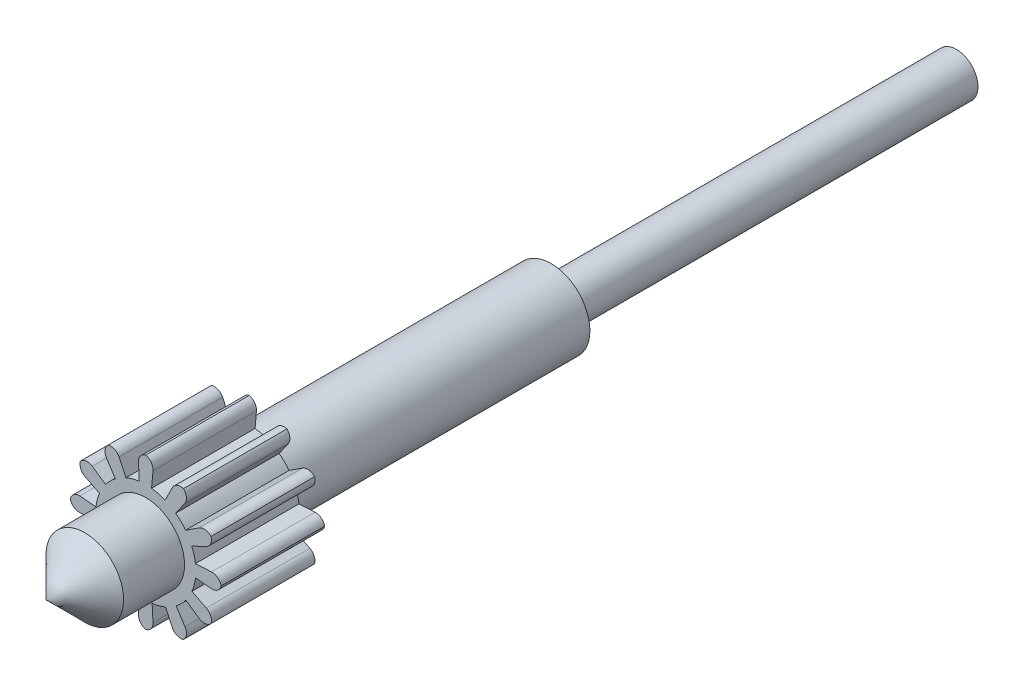
SolidWorks part; units mm, degrees
material "AISI 316 Stainless Steel Sheet (SS)"
ref_plane "Front Plane" through (0, 0, 0) normal (0, 0, 1) x (1, 0, 0)
ref_plane "Top Plane" through (0, 0, 0) normal (0, 1, 0) x (1, 0, 0)
ref_plane "Right Plane" through (0, 0, 0) normal (1, 0, 0) x (0, 0, -1)
sketch "Sketch1" plane through (0, 0, 0) normal (0, 0, 1) x (1, 0, 0)
  line L0 (0, 0) -> (0, 2.1618) construction
  line L1 (-0.1485, 1.153) -> (-0.1685, 1.5258)
  line L2 (0.1359, 1.1545) -> (0.1685, 1.5258)
  line L3 (0.4479, 1.0728) -> (0.617, 1.4056)
  line L4 (0.695, 0.9319) -> (0.9088, 1.2371)
  line L5 (0.9242, 0.7051) -> (1.2371, 0.9088)
  line L6 (1.0678, 0.4596) -> (1.4056, 0.617)
  line L7 (1.153, 0.1485) -> (1.5258, 0.1685)
  line L8 (1.1545, -0.1359) -> (1.5258, -0.1685)
  line L9 (1.0728, -0.4479) -> (1.4056, -0.617)
  line L10 (0.9319, -0.695) -> (1.2371, -0.9088)
  line L11 (0.7051, -0.9242) -> (0.9088, -1.2371)
  line L12 (0.4596, -1.0678) -> (0.617, -1.4056)
  line L13 (0.1485, -1.153) -> (0.1685, -1.5258)
  line L14 (-0.1359, -1.1545) -> (-0.1685, -1.5258)
  line L15 (-0.4479, -1.0728) -> (-0.617, -1.4056)
  line L16 (-0.695, -0.9319) -> (-0.9088, -1.2371)
  line L17 (-0.9242, -0.7051) -> (-1.2371, -0.9088)
  line L18 (-1.0678, -0.4596) -> (-1.4056, -0.617)
  line L19 (-1.153, -0.1485) -> (-1.5258, -0.1685)
  line L20 (-1.1545, 0.1359) -> (-1.5258, 0.1685)
  line L21 (-1.0728, 0.4479) -> (-1.4056, 0.617)
  line L22 (-0.9319, 0.695) -> (-1.2371, 0.9088)
  line L23 (-0.7051, 0.9242) -> (-0.9088, 1.2371)
  line L24 (-0.4596, 1.0678) -> (-0.617, 1.4056)
  arc A0 (-0.1485, 1.153) -> (-0.4596, 1.0678) centre (0, 0) ccw
  arc A1 (-0.7051, 0.9242) -> (-0.9319, 0.695) centre (0, 0) ccw
  arc A2 (0.4479, 1.0728) -> (0.1359, 1.1545) centre (0, 0) ccw
  arc A3 (-0.1685, 1.5258) -> (0, 1.75) centre (0.0494, 1.5375) cw
  arc A4 (0.1685, 1.5258) -> (0, 1.75) centre (-0.0494, 1.5375) ccw
  arc A5 (0.617, 1.4056) -> (0.875, 1.5155) centre (0.8115, 1.3068) cw
  arc A6 (0.9088, 1.2371) -> (0.875, 1.5155) centre (0.726, 1.3562) ccw
  arc A7 (1.2371, 0.9088) -> (1.5155, 0.875) centre (1.3562, 0.726) cw
  arc A8 (1.4056, 0.617) -> (1.5155, 0.875) centre (1.3068, 0.8115) ccw
  arc A9 (1.5258, 0.1685) -> (1.75, 0) centre (1.5375, -0.0494) cw
  arc A10 (1.5258, -0.1685) -> (1.75, 0) centre (1.5375, 0.0494) ccw
  arc A11 (1.4056, -0.617) -> (1.5155, -0.875) centre (1.3068, -0.8115) cw
  arc A12 (1.2371, -0.9088) -> (1.5155, -0.875) centre (1.3562, -0.726) ccw
  arc A13 (0.9088, -1.2371) -> (0.875, -1.5155) centre (0.726, -1.3562) cw
  arc A14 (0.617, -1.4056) -> (0.875, -1.5155) centre (0.8115, -1.3068) ccw
  arc A15 (0.1685, -1.5258) -> (0, -1.75) centre (-0.0494, -1.5375) cw
  arc A16 (-0.1685, -1.5258) -> (0, -1.75) centre (0.0494, -1.5375) ccw
  arc A17 (-0.617, -1.4056) -> (-0.875, -1.5155) centre (-0.8115, -1.3068) cw
  arc A18 (-0.9088, -1.2371) -> (-0.875, -1.5155) centre (-0.726, -1.3562) ccw
  arc A19 (-1.2371, -0.9088) -> (-1.5155, -0.875) centre (-1.3562, -0.726) cw
  arc A20 (-1.4056, -0.617) -> (-1.5155, -0.875) centre (-1.3068, -0.8115) ccw
  arc A21 (-1.5258, -0.1685) -> (-1.75, 0) centre (-1.5375, 0.0494) cw
  arc A22 (-1.5258, 0.1685) -> (-1.75, 0) centre (-1.5375, -0.0494) ccw
  arc A23 (-1.4056, 0.617) -> (-1.5155, 0.875) centre (-1.3068, 0.8115) cw
  arc A24 (-1.2371, 0.9088) -> (-1.5155, 0.875) centre (-1.3562, 0.726) ccw
  arc A25 (-0.9088, 1.2371) -> (-0.875, 1.5155) centre (-0.726, 1.3562) cw
  arc A26 (-0.617, 1.4056) -> (-0.875, 1.5155) centre (-0.8115, 1.3068) ccw
  arc A27 (0.9242, 0.7051) -> (0.695, 0.9319) centre (0, 0) ccw
  arc A28 (1.153, 0.1485) -> (1.0678, 0.4596) centre (0, 0) ccw
  arc A29 (-1.0728, 0.4479) -> (-1.1545, 0.1359) centre (0, 0) ccw
  arc A30 (-1.153, -0.1485) -> (-1.0678, -0.4596) centre (0, 0) ccw
  arc A31 (-0.9242, -0.7051) -> (-0.695, -0.9319) centre (0, 0) ccw
  arc A32 (-0.4479, -1.0728) -> (-0.1359, -1.1545) centre (0, 0) ccw
  arc A33 (0.1485, -1.153) -> (0.4596, -1.0678) centre (0, 0) ccw
  arc A34 (0.7051, -0.9242) -> (0.9319, -0.695) centre (0, 0) ccw
  arc A35 (1.0728, -0.4479) -> (1.1545, -0.1359) centre (0, 0) ccw
  circle A36 centre (0, 0) radius 0.9
  circle A37 centre (0, 0) radius 1.75
  point P93 (0, 0)
  dimension "D1" = 3.5
  dimension "D2" = 2.325
  dimension "D3" = 1.8
  dimension "D4" = 12
extrude "Boss-Extrude3" add sketch "Sketch1" along normal blind 2.4 contours A36 A3 L1 A0 L24 A26 A25 L23 A1 L22 A24 A23 L21 A29 L20 A22 A21 L19 A30 L18 A20 A19 L17 A31 L16 A18 A17 L15 A32 L14 A16 A15 L13 A33 L12 A14 A13 L11 A34 L10 A12 A11 L9 A35 L8 A10 A9 L7 A28 L6 region at (-0.1091, 1.342, 0)
extrude "Boss-Extrude4" add sketch "Sketch1<4>" along normal blind 4.7124 and the other way blind 7 contours A36 region at (0, 0, 0)
sketch "Sketch1<4>" plane through (0, 0, 0) normal (0, 0, 1) x (1, 0, 0) same geometry as "Sketch1"
sketch "Sketch2" plane through (0, 0, -7) normal (0, 0, -1) x (-1, 0, 0)
  circle A0 centre (0, 0) radius 0.5
  dimension "D1" = 1
extrude "Boss-Extrude5" add sketch "Sketch2" along normal blind 9.4
chamfer "Chamfer1" distance 0.9 angle 45 1 edges at (0.9, 0, 4.7124)
